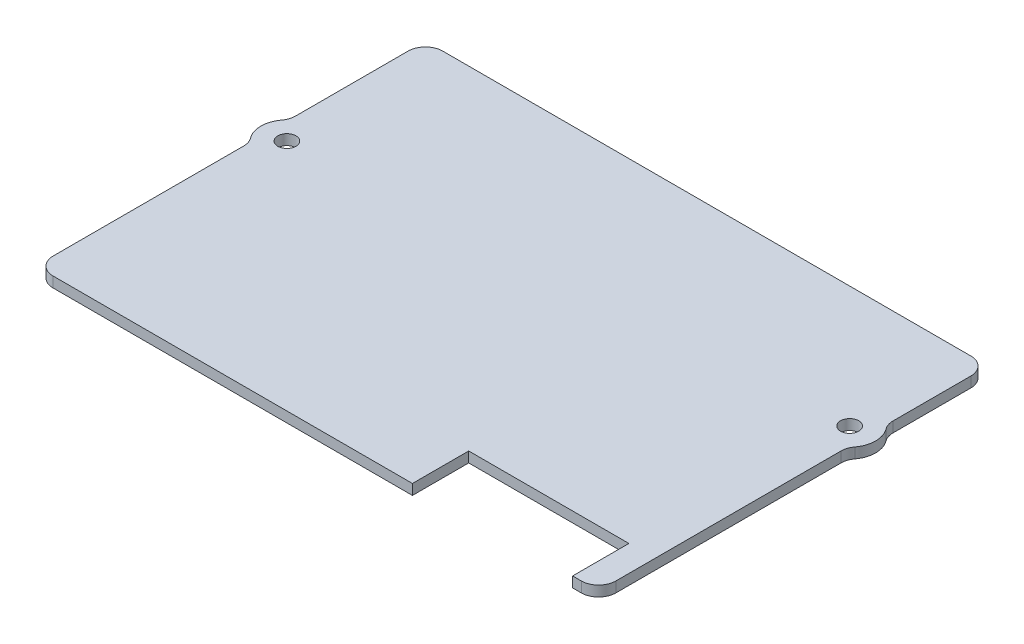
SolidWorks part; units mm, degrees
ref_plane "前视基准面" through (0, 0, 0) normal (0, 0, 1) x (1, 0, 0)
ref_plane "上视基准面" through (0, 0, 0) normal (0, 1, 0) x (1, 0, 0)
ref_plane "右视基准面" through (0, 0, 0) normal (1, 0, 0) x (0, 0, -1)
other "Configuration Table"
sketch "草图1" plane through (0, 0, 0) normal (0, 1, 0) x (1, 0, 0)
  line L1 (0, 0) -> (65, 0)
  line L2 (0, 0) -> (0, 45)
  line L3 (0, 45) -> (65, 45)
  line L4 (65, 0) -> (65, 45)
  dimension "D1" = 65
  dimension "D2" = 45
extrude "凸台-拉伸1" add sketch "草图1" along normal blind 1.2
fillet "圆角1" radius 2 4 edges at (0, 0.6, 0) (0, 0.6, -45) (65, 0.6, -45) (65, 0.6, 0)
sketch "草图2" plane through (0, 1.2, 0) normal (0, 1, 0) x (1, 0, 0)
  line L0 (63, 45) -> (2, 45) construction
  line L1 (65, 2) -> (65, 43) construction
  line L2 (0, 43) -> (0, 2) construction
  circle A0 centre (63, 31) radius 1.05
  circle A1 centre (2, 27) radius 1.05
  circle A2 centre (63, 31) radius 3
  circle A3 centre (2, 27) radius 3
  point P8 (63.0302, 31)
  dimension "D1" = 2.1
  dimension "D2" = 2.1
  dimension "D5" = 6
  dimension "D6" = 6
  dimension "D3" = 14
  dimension "D4" = 18
  dimension "D7" = 2
  dimension "D8" = 2
extrude "凸台-拉伸2" add sketch "草图2<5>" against normal blind 1.2 contours A3 | A2
sketch "草图2<5>" plane through (0, 1.2, 0) normal (0, 1, 0) x (1, 0, 0) same geometry as "草图2"
extrude "切除-拉伸1" cut sketch "草图2" against normal through all contours A1 | A0
fillet "圆角2" radius 2 4 edges at (65, 0.6, -28.7639) (65, 0.6, -33.2361) (0, 0.6, -24.7639) (0, 0.6, -29.2361)
sketch "草图3" plane through (0, 1.2, 0) normal (0, 1, 0) x (1, 0, 0)
  line L0 (2, 0) -> (63, 0) construction
  line L1 (43.5, 0) -> (62, 0)
  line L2 (43.5, 0) -> (43.5, 6.5)
  line L3 (43.5, 6.5) -> (62, 6.5)
  line L4 (62, 0) -> (62, 6.5)
  line L5 (65, 2) -> (65, 28) construction
  dimension "D1" = 18.5
  dimension "D2" = 6.5
  dimension "D3" = 3
extrude "切除-拉伸2" cut sketch "草图3" against normal through all
